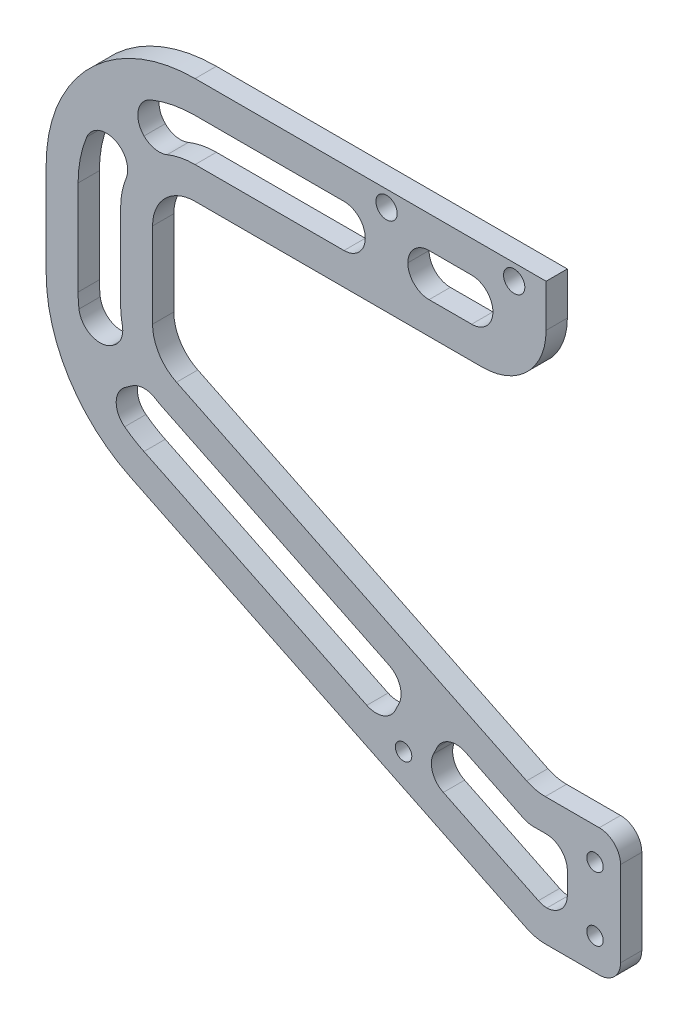
SolidWorks part; units mm, degrees
material "6061 Alloy"
ref_plane "Front Plane" through (0, 0, 0) normal (0, 0, 1) x (1, 0, 0)
ref_plane "Top Plane" through (0, 0, 0) normal (0, 1, 0) x (1, 0, 0)
ref_plane "Right Plane" through (0, 0, 0) normal (1, 0, 0) x (0, 0, -1)
sketch "Sketch1" plane through (0, 0, 0) normal (0, 0, 1) x (1, 0, 0)
  line L0 (0, 0) -> (0, 38.1)
  line L1 (0, 38.1) -> (-25.4, 38.1)
  line L2 (-139.7, 101.6) -> (-139.7, 127)
  line L3 (-127, 139.7) -> (-22.225, 139.7)
  line L4 (-22.225, 139.7) -> (-22.225, 171.45)
  line L5 (-22.225, 171.45) -> (-127, 171.45)
  line L6 (-171.45, 127) -> (-171.45, 98.8013)
  line L7 (0, 0) -> (-25.4, 0)
  line L8 (-146.4302, 58.8229) -> (-25.4, 0)
  line L9 (0, 19.05) -> (25.4, 19.05) construction
  line L10 (25.4, 19.05) -> (25.4, 120.65) construction
  line L11 (25.4, 120.65) -> (-127, 120.65) construction
  line L12 (-25.4, 38.1) -> (-132.5515, 90.1776)
  line L13 (0, 19.05) -> (-7.62, 19.05) construction
  line L14 (-7.62, 28.575) -> (-7.62, 9.525) construction
  line L15 (-7.62, 28.575) -> (-64.77, 28.575) construction
  line L16 (-69.85, 166.6875) -> (-31.75, 166.6875) construction
  line L17 (-50.8, 166.6875) -> (-50.8, 120.65) construction
  line L18 (-127, 120.65) -> (-127, 101.6) construction
  arc A0 (-171.45, 98.8013) -> (-146.4302, 58.8229) centre (-127, 98.8013) ccw
  arc A1 (-127, 171.45) -> (-171.45, 127) centre (-127, 127) ccw
  arc A2 (-139.7, 127) -> (-127, 139.7) centre (-127, 127) cw
  arc A3 (-132.5515, 90.1776) -> (-139.7, 101.6) centre (-127, 101.6) cw
  circle A7 centre (-31.75, 166.6875) radius 3.175 construction
  circle A8 centre (-69.85, 166.6875) radius 3.175 construction
  point P10 (0, 0)
  point P26 (-50.8, 166.6875)
  point P28 (-50.8, 120.65)
  dimension "D9" = 44.45
  dimension "D10" = 12.7
  dimension "D22" = 6.35
  dimension "D8" = 44.45
  dimension "D1" = 38.1
  dimension "D3" = 31.75
  dimension "D4" = 31.75
  dimension "D5" = 19.05
  dimension "D6" = 19.05
  dimension "D7" = 57.15
  dimension "D11" = 25.4
  dimension "D12" = 101.6
  dimension "D13" = 152.4
  dimension "D14" = 25.4
  dimension "D15" = 19.05
  dimension "D17" = 7.62
  dimension "D19" = 4.7625
  dimension "D20" = 38.1
  dimension "D21" = 9.525
extrude "Boss-Extrude1" add sketch "Sketch1" along normal blind 6.35
hole_wizard "1/4 (0.25) Diameter Hole1" positions "Sketch3" profile "Sketch2" hole size "1/4" standard "ANSI Inch"
sketch "Sketch3" plane through (0, 0, 6.35) normal (0, 0, 1) x (1, 0, 0)
  line L0 (-69.85, 166.6875) -> (-22.225, 166.6875) construction
  line L1 (-22.225, 139.7) -> (-22.225, 171.45) construction
  line L3 (-22.225, 171.45) -> (-127, 171.45) construction
  point P4 (-69.85, 166.6875)
  point P6 (-31.75, 166.6875)
  dimension "D1" = 9.525
  dimension "D2" = 38.1
  dimension "D3" = 4.7625
sketch "Sketch2" plane through (-69.85, 166.6875, 6.35) normal (1, 0, 0) x (0, -1, 0)
  line L0 (0, 0) -> (0, 11.5597)
  line L1 (0, 11.5597) -> (3.175, 9.652)
  line L2 (3.175, 9.652) -> (3.175, 0)
  line L5 (3.175, 0) -> (0, 0)
  line L10 (0, 11.5597) -> (-3.175, 9.652) construction
  line L11 (0, -6.35) -> (0, 107.95) construction
  dimension "Hole Dia." = 6.35
  dimension "Hole Depth" = 9.652
  dimension "Drill Angle" = 118
hole_wizard "#10 (0.1935) Diameter Hole1" positions "Sketch5" profile "Sketch4" hole size "#10" standard "ANSI Inch"
sketch "Sketch5" plane through (0, 0, 6.35) normal (0, 0, 1) x (1, 0, 0)
  line L0 (-7.62, 28.575) -> (-7.62, 9.525) construction
  line L2 (0, 19.05) -> (-7.62, 19.05) construction
  line L3 (0, 0) -> (0, 38.1) construction
  line L6 (-64.77, 28.575) -> (-7.62, 28.575) construction
  point P0 (-7.62, 28.575)
  point P2 (-7.62, 9.525)
  point P18 (-64.77, 28.575)
  dimension "D1" = 19.05
  dimension "D2" = 7.62
  dimension "D3" = 57.15
sketch "Sketch4" plane through (-7.62, 28.575, 6.35) normal (1, 0, 0) x (0, -1, 0)
  line L0 (0, 0) -> (0, 11.1286)
  line L1 (0, 11.1286) -> (2.4574, 9.652)
  line L2 (2.4574, 9.652) -> (2.4574, 0)
  line L5 (2.4574, 0) -> (0, 0)
  line L10 (0, 11.1286) -> (-2.4575, 9.652) construction
  line L11 (0, -6.35) -> (0, 107.95) construction
  dimension "Hole Dia." = 4.9149
  dimension "Hole Depth" = 9.652
  dimension "Drill Angle" = 118
fillet "Fillet1" radius 12.7 2 edges at (-25.4, 0, 3.175) (-25.4, 38.1, 3.175)
fillet "Fillet2" radius 6.35 2 edges at (0, 0, 3.175) (0, 38.1, 3.175)
sketch "Sketch7" plane through (0, 0, 6.35) normal (0, 0, 1) x (1, 0, 0)
  line L0 (-12.7, 28.575) -> (-22.4772, 28.575)
  line L1 (-32.1924, 30.8108) -> (-51.9549, 40.4158)
  line L2 (-58.6067, 26.7295) -> (-23.8651, 9.8444)
  line L3 (-22.4772, 9.525) -> (-12.7, 9.525)
  line L4 (-12.7, 28.575) -> (-12.7, 9.525)
  line L5 (-58.6067, 26.7295) -> (-51.9549, 40.4158)
  line L6 (-32.1924, 30.8108) -> (-136.7151, 81.6108) construction
  line L7 (-142.2666, 67.3897) -> (-23.8651, 9.8444) construction
  line L8 (-22.4772, 9.525) -> (-6.35, 9.525) construction
  line L9 (-6.35, 28.575) -> (-22.4772, 28.575) construction
  line L10 (-22.4772, 0) -> (-6.35, 0)
  line L11 (0, 6.35) -> (0, 31.75)
  line L12 (-6.35, 38.1) -> (-22.4772, 38.1)
  line L13 (-28.0287, 39.3776) -> (-132.5515, 90.1776)
  line L14 (-139.7, 101.6) -> (-139.7, 127)
  line L15 (-127, 139.7) -> (-22.225, 139.7)
  line L16 (-22.225, 139.7) -> (-22.225, 171.45)
  line L17 (-22.225, 171.45) -> (-127, 171.45)
  line L18 (-171.45, 127) -> (-171.45, 98.8013)
  line L19 (-146.4302, 58.8229) -> (-28.0287, 1.2776)
  line L20 (-161.925, 133.35) -> (-161.925, 95.25)
  line L21 (0, 6.35) -> (0, 31.75) construction
  line L22 (-161.925, 95.25) -> (-149.225, 95.25)
  line L23 (-149.225, 133.35) -> (-149.225, 95.25)
  line L24 (-139.7, 101.6) -> (-139.7, 127) construction
  line L25 (-127, 139.7) -> (-22.225, 139.7) construction
  line L26 (-22.225, 139.7) -> (-22.225, 171.45) construction
  line L27 (-22.225, 171.45) -> (-127, 171.45) construction
  line L28 (-171.45, 127) -> (-171.45, 98.8013) construction
  line L29 (-149.225, 133.35) -> (-161.925, 133.35)
  line L30 (-133.35, 158.75) -> (-133.35, 146.05)
  line L31 (-133.35, 146.05) -> (-79.375, 146.05)
  line L32 (-79.375, 146.05) -> (-79.375, 158.75)
  line L33 (-28.0287, 39.3776) -> (-132.5515, 90.1776) construction
  line L34 (-28.0287, 39.3776) -> (-132.5515, 90.1776)
  line L35 (-79.375, 158.75) -> (-133.35, 158.75)
  line L36 (-28.0287, 39.3776) -> (-132.5515, 90.1776) construction
  line L37 (-146.4302, 58.8229) -> (-28.0287, 1.2776) construction
  line L38 (-22.4772, 0) -> (-6.35, 0) construction
  line L39 (-6.35, 38.1) -> (-22.4772, 38.1) construction
  line L40 (-60.325, 158.75) -> (-60.325, 146.05)
  line L41 (-60.325, 146.05) -> (-41.275, 146.05)
  line L42 (-41.275, 146.05) -> (-41.275, 158.75)
  line L43 (-41.275, 158.75) -> (-60.325, 158.75)
  line L49 (-131.9116, 79.2762) -> (-63.3773, 45.9673)
  line L50 (-63.3773, 45.9673) -> (-70.0291, 32.281)
  line L51 (-70.0291, 32.281) -> (-138.5634, 65.5899)
  line L52 (-138.5634, 65.5899) -> (-131.9116, 79.2762)
  line L53 (-146.4302, 58.8229) -> (-28.0287, 1.2776) construction
  line L54 (-58.6067, 26.7295) -> (-70.0291, 32.281) construction
  line L55 (-64.77, 28.575) -> (-53.5025, 51.7583) construction
  arc A0 (-32.1924, 30.8108) -> (-22.4772, 28.575) centre (-22.4772, 50.8) ccw
  arc A1 (-23.8651, 9.8444) -> (-22.4772, 9.525) centre (-22.4772, 12.7) ccw
  circle A2 centre (-69.85, 166.6875) radius 3.175 construction
  circle A3 centre (-31.75, 166.6875) radius 3.175 construction
  arc A8 (-6.35, 0) -> (0, 6.35) centre (-6.35, 6.35) ccw
  arc A9 (0, 31.75) -> (-6.35, 38.1) centre (-6.35, 31.75) ccw
  arc A10 (-28.0287, 39.3776) -> (-22.4772, 38.1) centre (-22.4772, 50.8) ccw
  arc A11 (-139.7, 101.6) -> (-132.5515, 90.1776) centre (-127, 101.6) ccw
  arc A12 (-127, 139.7) -> (-139.7, 127) centre (-127, 127) ccw
  arc A13 (-127, 171.45) -> (-171.45, 127) centre (-127, 127) ccw
  arc A14 (-171.45, 98.8013) -> (-146.4302, 58.8229) centre (-127, 98.8013) ccw
  arc A15 (-28.0287, 1.2776) -> (-22.4772, 0) centre (-22.4772, 12.7) ccw
  arc A16 (-6.35, 0) -> (0, 6.35) centre (-6.35, 6.35) ccw construction
  arc A17 (0, 31.75) -> (-6.35, 38.1) centre (-6.35, 31.75) ccw construction
  arc A18 (-28.0287, 39.3776) -> (-22.4772, 38.1) centre (-22.4772, 50.8) ccw construction
  arc A19 (-139.7, 101.6) -> (-132.5515, 90.1776) centre (-127, 101.6) ccw construction
  arc A20 (-127, 139.7) -> (-139.7, 127) centre (-127, 127) ccw construction
  arc A21 (-127, 171.45) -> (-171.45, 127) centre (-127, 127) ccw construction
  arc A22 (-171.45, 98.8013) -> (-146.4302, 58.8229) centre (-127, 98.8013) ccw construction
  arc A23 (-28.0287, 1.2776) -> (-22.4772, 0) centre (-22.4772, 12.7) ccw construction
  point P46 (-64.3179, 29.5052)
  point P63 (-149.225, 114.3)
  point P64 (-139.7, 114.3)
  dimension "D11" = 9.525
  dimension "D3" = 9.525
  dimension "D4" = 9.525
  dimension "D5" = 12.7
  dimension "D6" = 12.7
  dimension "D7" = 76.2
  dimension "D8" = 38.1
  dimension "D9" = 9.525
  dimension "D10" = 9.525
  dimension "D12" = 9.525
  dimension "D13" = 6.35
  dimension "D14" = 12.7
  dimension "D15" = 9.525
  dimension "D16" = 53.975
  dimension "D1" = 0
  dimension "D2" = 9.525
extrude "Cut-Extrude2" [suppressed] cut sketch "Sketch7" against normal up to next contours L52 L51 L50 L49 | L23 L29 L20 L22 | L32 L35 L30 L31 | L42 L43 L40 L41 | L5 L1 A0 L0 L4 L3 A1 L2
fillet "Fillet3" [suppressed] radius 6.35
sketch "Sketch8" plane through (0, 0, 6.35) normal (0, 0, 1) x (1, 0, 0)
  line L0 (-158.4309, 158.4309) -> (-135.9803, 135.9803) construction
  line L1 (-164.6794, 75.2203) -> (-137.4037, 94.3163) construction
  line L2 (-53.5025, 51.7583) -> (-68.4815, 20.9384) construction
  line L3 (-28.0287, 39.3776) -> (-132.5515, 90.1776) construction
  line L4 (-146.4302, 58.8229) -> (-28.0287, 1.2776) construction
  line L5 (-123.6324, 130.3676) -> (-130.3676, 123.6324) construction
  line L6 (-101.6, 171.45) -> (-101.6, 161.925) construction
  line L7 (-22.225, 171.45) -> (-127, 171.45) construction
  line L8 (-101.6, 139.7) -> (-101.6, 149.225) construction
  line L9 (-127, 139.7) -> (-22.225, 139.7) construction
  line L10 (-76.2, 161.925) -> (-127, 161.925)
  line L11 (-127, 149.225) -> (-76.2, 149.225)
  line L12 (-76.2, 149.225) -> (-76.2, 161.925)
  line L13 (-148.0974, 154.8326) -> (-138.9828, 145.718)
  line L14 (-69.85, 171.45) -> (-69.85, 139.7) construction
  line L15 (-31.75, 171.45) -> (-31.75, 139.7) construction
  line L16 (-161.925, 127) -> (-161.925, 98.8013)
  line L17 (-149.225, 127) -> (-149.225, 101.6)
  line L18 (-154.8326, 148.0974) -> (-145.718, 138.9828)
  line L19 (-153.5499, 88.8258) -> (-148.0871, 81.023) construction
  line L20 (-159.0667, 84.9635) -> (-147.515, 93.0509)
  line L21 (-142.0522, 85.2482) -> (-154.1221, 76.7979)
  line L22 (-136.7151, 81.6108) -> (-63.3773, 45.9673)
  line L23 (-142.2666, 67.3897) -> (-70.0291, 32.281)
  line L24 (-70.4812, 31.3507) -> (-59.0588, 25.7993) construction
  line L25 (-70.0291, 32.281) -> (-63.3773, 45.9673)
  line L26 (-76.2, 155.575) -> (-63.5, 155.575) construction
  line L27 (-51.9549, 40.4158) -> (-27.5921, 28.575)
  line L28 (-27.5921, 28.575) -> (-15.875, 28.575)
  line L29 (-15.875, 28.575) -> (-15.875, 9.525)
  line L30 (-15.875, 9.525) -> (-23.2079, 9.525)
  line L31 (-23.2079, 9.525) -> (-58.6067, 26.7295)
  line L32 (-58.6067, 26.7295) -> (-51.9549, 40.4158)
  line L34 (0, 6.35) -> (0, 31.75) construction
  line L35 (-15.875, 9.525) -> (-15.875, 0) construction
  line L36 (-22.4772, 0) -> (-6.35, 0) construction
  line L37 (-15.875, 28.575) -> (-15.875, 38.1) construction
  line L38 (-6.35, 38.1) -> (-22.4772, 38.1) construction
  line L39 (-38.1, 155.575) -> (-25.4, 155.575) construction
  line L41 (-63.5, 161.925) -> (-38.1, 161.925)
  line L42 (-63.5, 161.925) -> (-63.5, 149.225)
  line L43 (-63.5, 149.225) -> (-38.1, 149.225)
  line L44 (-38.1, 161.925) -> (-38.1, 149.225)
  arc A0 (-127, 171.45) -> (-171.45, 127) centre (-127, 127) ccw construction
  arc A1 (-127, 139.7) -> (-139.7, 127) centre (-127, 127) ccw construction
  arc A2 (-171.45, 98.8013) -> (-146.4302, 58.8229) centre (-127, 98.8013) ccw construction
  arc A3 (-139.7, 101.6) -> (-132.5515, 90.1776) centre (-127, 101.6) ccw construction
  arc A4 (-127, 149.225) -> (-138.9828, 145.718) centre (-127, 127) ccw
  arc A5 (-127, 161.925) -> (-148.0974, 154.8326) centre (-127, 127) ccw
  arc A6 (-145.718, 138.9828) -> (-149.225, 127) centre (-127, 127) ccw
  arc A7 (-154.8326, 148.0974) -> (-161.925, 127) centre (-127, 127) ccw
  arc A8 (-149.225, 101.6) -> (-147.515, 93.0509) centre (-127, 101.6) ccw
  arc A9 (-161.925, 98.8013) -> (-159.0667, 84.9635) centre (-127, 98.8013) ccw
  arc A10 (-142.0522, 85.2482) -> (-136.7151, 81.6108) centre (-127, 101.6) ccw
  arc A11 (-154.1221, 76.7979) -> (-142.2666, 67.3897) centre (-127, 98.8013) ccw
  point P8 (-127, 127)
  point P9 (-127, 127)
  point P18 (-127, 101.6)
  point P19 (-150.8185, 84.9244)
  point P26 (-64.77, 28.575)
  point P47 (-69.85, 166.6875)
  point P48 (-31.75, 166.6875)
  point P77 (-69.85, 155.575)
  point P94 (-31.75, 155.575)
  dimension "D1" = 9.525
  dimension "D2" = 9.525
  dimension "D3" = 12.7
  dimension "D4" = 12.7
  dimension "D5" = 15.875
extrude "Cut-Extrude3" cut sketch "Sketch8" against normal through all
fillet "Fillet4" radius 6.35 22 edges at (-27.5921, 28.575, 3.175) (-23.2079, 9.525, 3.175) (-15.875, 9.525, 3.175) (-15.875, 28.575, 3.175) (-58.6067, 26.7295, 3.175) (-51.9549, 40.4158, 3.175) (-63.3773, 45.9673, 3.175) (-70.0291, 32.281, 3.175) (-154.1221, 76.7979, 3.175) (-142.0522, 85.2482, 3.175) (-147.515, 93.0509, 3.175) (-159.0667, 84.9635, 3.175) (-154.8326, 148.0974, 3.175) (-145.718, 138.9828, 3.175) (-138.9828, 145.718, 3.175) (-148.0974, 154.8326, 3.175) (-76.2, 149.225, 3.175) (-76.2, 161.925, 3.175) (-38.1, 149.225, 3.175) (-38.1, 161.925, 3.175) (-63.5, 149.225, 3.175) (-63.5, 161.925, 3.175)
fillet "Fillet5" radius 19.05 1 edges at (-22.225, 139.7, 3.175)
